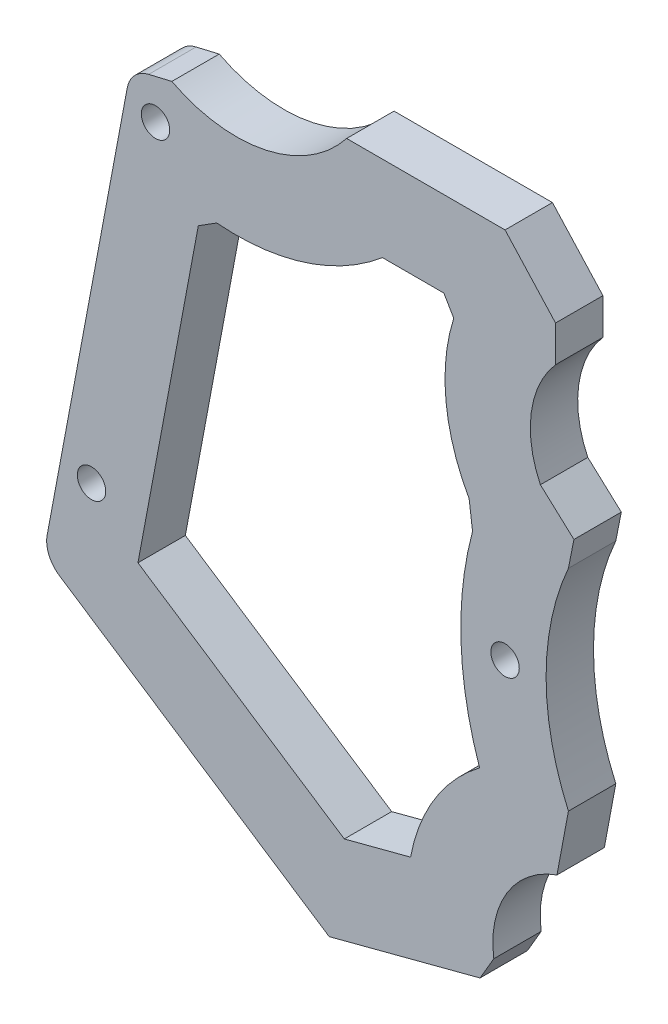
SolidWorks part; units mm, degrees
material "PMMA"
ref_plane "Front Plane" through (0, 0, 0) normal (0, 0, 1) x (1, 0, 0)
ref_plane "Top Plane" through (0, 0, 0) normal (0, 1, 0) x (1, 0, 0)
ref_plane "Right Plane" through (0, 0, 0) normal (1, 0, 0) x (0, 0, -1)
sketch "Sketch2" plane through (0, 0, -29.5) normal (0, 0, 1) x (1, 0, 0)
  line L0 (-2.6246, 3.5489) -> (-11.8012, -45.4263)
  line L1 (-11.8012, -45.4263) -> (18.322, -65.2757)
  line L2 (18.322, -65.2757) -> (36.1765, -60.5877)
  line L4 (42.3608, -47.6207) -> (43.5671, -41.1827)
  line L7 (42.2105, 2.7425) -> (36.882, 8.5851)
  line L8 (36.882, 8.5851) -> (20.1673, 8.5851)
  line L9 (1.7237, 4.5758) -> (-2.6246, 3.5489)
  line L12 (42.2105, -1.0713) -> (42.2105, 2.7425)
  line L13 (40.6105, -12.8376) -> (44.1484, -16.0679)
  line L14 (44.1484, -16.0679) -> (43.5671, -18.9936)
  line L15 (-1.8533, -41.2031) -> (19.9206, -55.5509)
  line L16 (19.9206, -55.5509) -> (26.9126, -53.715)
  line L17 (34.1934, -41.9175) -> (34.1934, -41.9175)
  line L22 (30.4305, -0.4149) -> (23.9343, -0.4149)
  line L24 (4.5144, -7.2187) -> (-1.8533, -41.2031)
  line L25 (4.5144, -7.2187) -> (6.4642, -5.9882)
  line L26 (4.7837, -5.7819) -> (-1.8533, -41.2031) construction
  line L27 (4.7837, -5.7819) -> (4.7837, -5.7819) construction
  line L28 (30.4305, -0.4149) -> (31.4693, -2.1982)
  line L29 (32.1294, -0.4149) -> (23.9343, -0.4149) construction
  line L30 (32.1294, -0.4149) -> (32.1294, -0.4149) construction
  line L31 (32.1294, -0.4149) -> (32.1294, -0.4149) construction
  line L32 (33.4526, -20.6805) -> (33.0924, -17.8756)
  line L34 (33.4526, -18.4892) -> (33.9617, -18.954) construction
  line L35 (33.9617, -18.954) -> (33.9617, -18.954) construction
  circle A0 centre (0, 0) radius 1.5
  circle A1 centre (36.882, -30.72) radius 1.5
  circle A2 centre (-6.7526, -36.3786) radius 1.5
  arc A3 (36.1765, -60.5877) -> (42.3608, -47.6207) centre (45.7521, -57.1963) cw
  arc A4 (43.5671, -41.1827) -> (43.5671, -18.9936) centre (68.5341, -30.0882) cw
  arc A5 (40.6105, -12.8376) -> (42.2105, -1.0713) centre (50.3336, -8.1679) cw
  arc A6 (1.7237, 4.5758) -> (20.1673, 8.5851) centre (8.5221, 17.7286) ccw
  arc A7 (26.9126, -53.715) -> (34.1934, -41.9175) centre (45.7521, -57.1963) cw
  arc A8 (34.1934, -41.9175) -> (33.4526, -20.6805) centre (68.5341, -30.0882) cw
  arc A9 (33.0924, -17.8756) -> (31.4693, -2.1982) centre (50.3336, -8.1679) cw
  arc A10 (6.4642, -5.9882) -> (23.9343, -0.4149) centre (8.5221, 17.7286) ccw
  arc A11 (4.7837, -5.7819) -> (23.9343, -0.4149) centre (8.5221, 17.7286) ccw construction
  arc A12 (33.4526, -18.4892) -> (32.1294, -0.4149) centre (50.3336, -8.1679) cw construction
  arc A13 (34.1934, -41.9175) -> (33.9617, -18.954) centre (68.5341, -30.0882) cw construction
  dimension "D1" = 3
  dimension "D2" = 9
extrude "Boss-Extrude1" add sketch "Sketch2" along normal blind 5
fillet "Fillet1" radius 3 2 edges at (-2.6246, 3.5489, -27) (-11.8012, -45.4263, -27)
chamfer "Chamfer3" distance 2 angle 45 1 edges at (36.1765, -60.5877, -27) first distance on face at (27.2493, -62.9317, -27)
